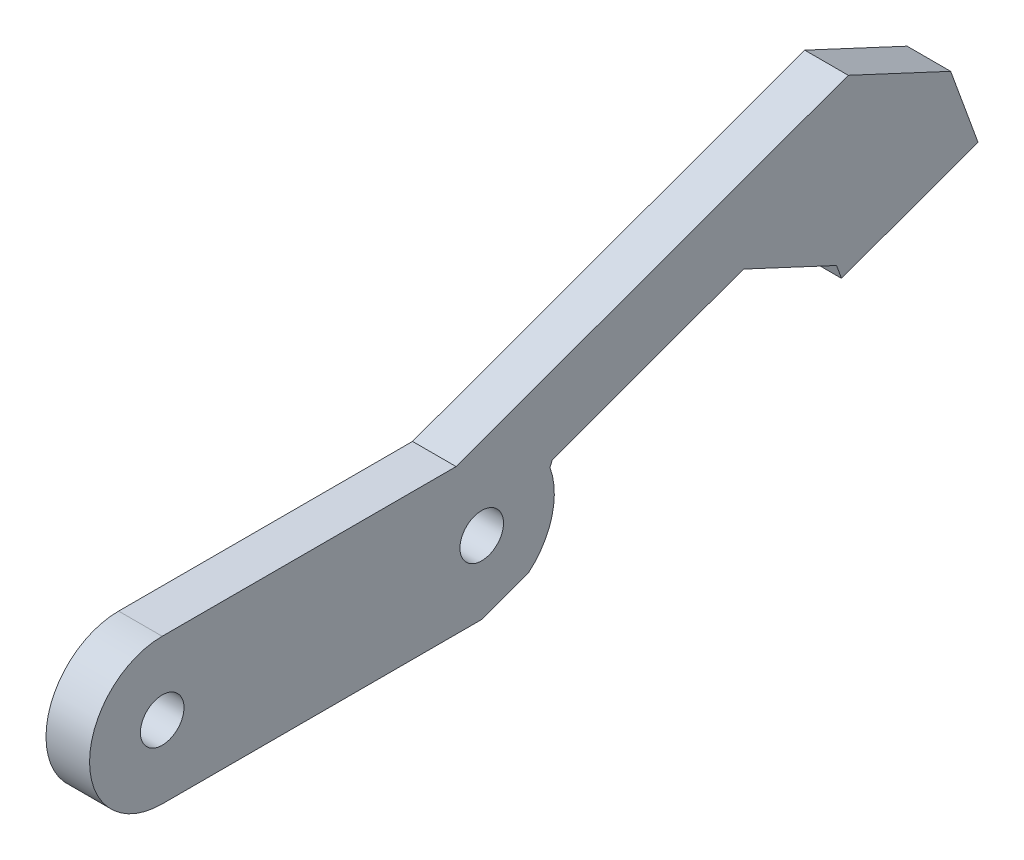
SolidWorks part; units mm, degrees
ref_plane "Front Plane" through (0, 0, 0) normal (0, 0, 1) x (1, 0, 0)
ref_plane "Top Plane" through (0, 0, 0) normal (0, 1, 0) x (1, 0, 0)
ref_plane "Right Plane" through (0, 0, 0) normal (1, 0, 0) x (0, 0, -1)
sketch "Sketch1" plane through (0, 0, 0) normal (1, 0, 0) x (0, 0, -1)
  line L1 (0, 0) -> (27, 0)
  line L2 (0, 0) -> (0, 10)
  line L3 (0, 10) -> (27, 10)
  circle A0 centre (5, 5) radius 1.5
  circle A1 centre (5, 5) radius 5
  circle A2 centre (27, 5) radius 5
  circle A3 centre (27, 5) radius 1.5
  dimension "D7" = 3
  dimension "D11" = 10
  dimension "D2" = 3
  dimension "D1" = 10
  dimension "D8" = 5
  dimension "D9" = 5
  dimension "D10" = 22
extrude "Boss-Extrude1" add sketch "Sketch1" along normal blind 3 contours A1 A0 | A2 L3 A1 L1 | A2 A3 region at (0, 5, -16) region at (0, 1.5645, -1.5645) region at (0, 5, -22.1414)
sketch "Sketch2" plane through (3, 0, 0) normal (1, 0, 0) x (0, 0, -1)
  line L0 (27, 0) -> (60.8289, 12.3127)
  line L1 (5, 0) -> (27, 0) construction
  line L3 (60.8289, 12.3127) -> (57.4087, 21.7097)
  line L5 (57.4087, 21.7097) -> (25.2367, 10)
  line L6 (5, 10) -> (27, 10) construction
  line L7 (31.8677, 7.0926) -> (45.0234, 11.8809)
  line L8 (31.8677, 7.0926) -> (28.8794, 0.684)
  line L9 (45.0234, 11.8809) -> (51.432, 8.8925)
  line L10 (51.432, 8.8925) -> (60.8289, 12.3127)
  line L11 (51.432, 8.8925) -> (51.774, 7.9528)
  line L12 (60.8289, 12.3127) -> (61.171, 11.373)
  line L13 (51.774, 7.9528) -> (61.171, 11.373)
  line L14 (5, 10) -> (27, 10)
  arc A0 (5, 10) -> (5, 0) centre (5, 5) ccw construction
  arc A2 (5, 10) -> (5, 0) centre (5, 5) ccw construction
  arc A3 (27, 0) -> (27, 10) centre (27, 5) ccw construction
  arc A4 (27, 0) -> (27, 10) centre (27, 5) ccw
  line M1 (27, 10) -> (5, 10)
  arc M4 (27, 0) -> (27, 10) centre (27, 5) ccw
  dimension "D1" = 160
  dimension "D2" = 36
  dimension "D3" = 90
  dimension "D4" = 10
  dimension "D5" = 10
  dimension "D6" = 45
  dimension "D7" = 45
  dimension "D8" = 5
  dimension "D9" = 5
  dimension "D10" = 14
  dimension "D11" = 1
extrude "Boss-Extrude2" add sketch "Sketch2" against normal blind 3 contours L7 L9 L0 L3 L5 L8 M1 M4 | L11 L13 L12 L0 region at (3, 13.7272, -46.7622) region at (3, 10.1328, -56.3015)
sketch "Sketch3" plane through (3, 0, 0) normal (1, 0, 0) x (0, 0, -1)
  line L0 (51.432, 8.8925) -> (27, 0)
  line L1 (5, 0) -> (27, 0) construction
  circle A0 centre (27, 5) radius 5
  arc M4 (27, 0) -> (31.6945, 6.721) centre (27, 5) ccw
  dimension "D1" = 160
extrude "Cut-Extrude1" cut sketch "Sketch3" against normal blind 3 contours L0 M4 region at (3, 0.4712, -28.6483)
sketch "Sketch4" plane through (3, 0, 0) normal (1, 0, 0) x (0, 0, -1)
  line L0 (52.2404, 19.8285) -> (59.2898, 16.5413)
  line L1 (57.4087, 21.7097) -> (25.2367, 10) construction
  line L2 (61.171, 11.373) -> (57.4087, 21.7097) construction
  line L3 (45.0234, 11.8809) -> (51.432, 8.8925) construction
  line L4 (57.4087, 21.7097) -> (25.2367, 10)
  line L5 (61.171, 11.373) -> (57.4087, 21.7097)
  line M8 (61.171, 11.373) -> (57.4087, 21.7097)
  line M9 (57.4087, 21.7097) -> (25.2367, 10)
extrude "Cut-Extrude2" cut sketch "Sketch4" against normal through all contours L0 M9 M8 region at (3, 19.3598, -56.313)
